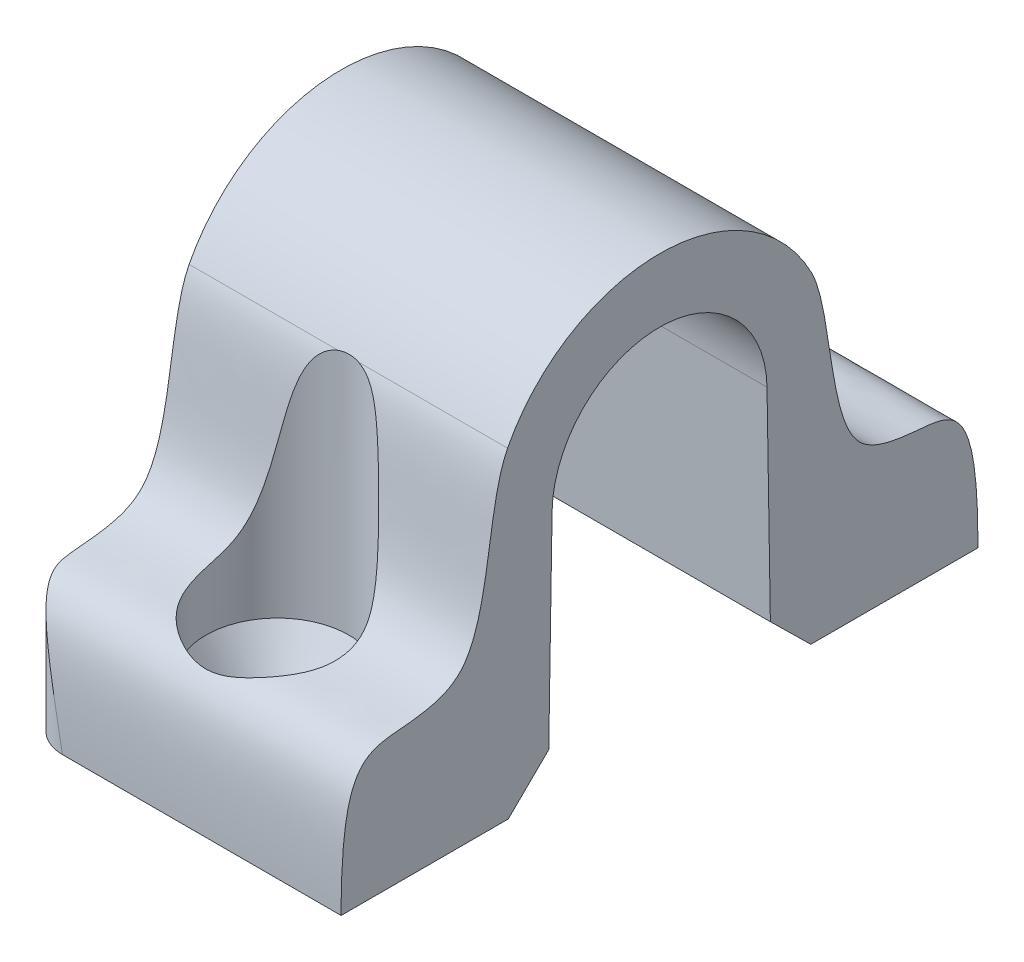
SolidWorks part; units mm, degrees
ref_plane "Front Plane" through (0, 0, 0) normal (0, 0, 1) x (1, 0, 0)
ref_plane "Top Plane" through (0, 0, 0) normal (0, 1, 0) x (1, 0, 0)
ref_plane "Right Plane" through (0, 0, 0) normal (1, 0, 0) x (0, 0, -1)
sketch "Sketch1" plane through (0, 0, 0) normal (1, 0, 0) x (0, 0, -1)
  line L0 (-20, -6.9546) -> (-20, 6.9546) construction
  line L1 (-20, 0) -> (-9.5, 0)
  line L3 (-6.9592, 2.4997) -> (-6.7491, 15.3602)
  line L4 (9.5, 0) -> (20, 0)
  line L5 (6.7491, 15.3602) -> (6.9592, 2.4997)
  line L6 (-7, 0) -> (7, 0) construction
  line L7 (0, 22) -> (0, 0) construction
  line L8 (-9.5, 0) -> (-6.9592, 2.4997)
  line L9 (6.9592, 2.4997) -> (9.5, 0)
  arc A0 (9.5466, 20.1922) -> (-9.5466, 20.1922) centre (0, 15.25) ccw
  arc A1 (6.7491, 15.3602) -> (-6.7491, 15.3602) centre (0, 15.25) ccw
  spline S0 degree 3 poles (-9.5466, 20.1922) (-10.8579, 17.6592) (-10.506, 9.8915) (-17.5342, 7.3235) (-20, 9.8125) (-20, 0) knots 0 0 0 0 0.359294 0.459294 1 1 1 1
  spline S1 degree 3 poles (9.5466, 20.1922) (10.8579, 17.6592) (10.506, 9.8915) (17.5342, 7.3235) (20, 9.8125) (20, 0) knots 0 0 0 0 0.359294 0.459294 1 1 1 1
  point P1 (0, 0)
  point P15 (-14.7484, 11.5439)
  point P16 (0, 0)
  point P17 (-15.6801, 12.9516)
  point P22 (-14.4995, 11.2224)
  point P23 (-15.9153, 8.3536)
  point P25 (-13.2037, 8.9922)
  dimension "D1" = 6.75
  dimension "D4" = 4
  dimension "D2" = 14
  dimension "D3" = 22
  dimension "D5" = 40
extrude "Boss-Extrude1" add sketch "Sketch1" along normal blind 10 and the other way blind 10
sketch "Sketch4" plane through (0, 0, 0) normal (1, 0, 0) x (0, 0, -1)
  line L0 (-12.1, 1) -> (-9.5, 5)
  line L2 (-9.5, 5) -> (-9.5, 20.2812)
  line L3 (-9.5, 20.2812) -> (-14, 20.2812)
  line L4 (-14, 20.2812) -> (-14, 0)
  line L5 (-12.1, 1) -> (-12.1, 0)
  line L6 (-20, 0) -> (-9.5, 0) construction
  line L7 (-12.1, 0) -> (-15.9, 0) construction
  line L9 (-14, 0) -> (-12.1, 0)
  arc A0 (9.5466, 20.1922) -> (-9.5466, 20.1922) centre (0, 15.25) ccw construction
  point P2 (0, 0)
  point P3 (0, 0)
  point P4 (-11.2665, 17.9064)
  point P8 (0, 0)
  point P9 (0, 0)
  point P10 (0, 0)
  point P11 (0, 0)
  point P15 (0, 0)
  point P16 (0, 0)
  point P17 (0, 0)
  point P18 (-14.1133, 0)
  point P20 (-14.1494, 0)
  dimension "D1" = 1.9
  dimension "D2" = 4.5
  dimension "D3" = 4
  dimension "D4" = 1
revolve "Cut-Revolve1" cut sketch "Sketch4" angle 360 about L4
mirror "Mirror1" about plane through (0, 0, 0) normal (0, 0, 1) of "Cut-Revolve1"
sketch "Sketch5" plane through (0, 0, 0) normal (0, -1, 0) x (1, 0, 0)
  line L0 (-10, 20) -> (10, 20) construction
  line L2 (-10, 20) -> (-10, 9.5) construction
  line L3 (-7.5, 20) -> (-10, 20)
  line L4 (-10, 20) -> (-10, 17.5)
  line L5 (-10, 0) -> (10, 0) construction
  line L6 (-10, 6.7491) -> (-10, -6.7491) construction
  line L7 (10, -6.7491) -> (10, 6.7491) construction
  line L8 (-10, -20) -> (-10, -17.5)
  line L9 (-7.5, -20) -> (-10, -20)
  arc A0 (-7.5, 20) -> (-10, 17.5) centre (-7.5, 17.5) ccw
  arc A1 (-7.5, -20) -> (-10, -17.5) centre (-7.5, -17.5) cw
  dimension "D1" = 5
extrude "Cut-Extrude1" cut sketch "Sketch5" against normal through all
